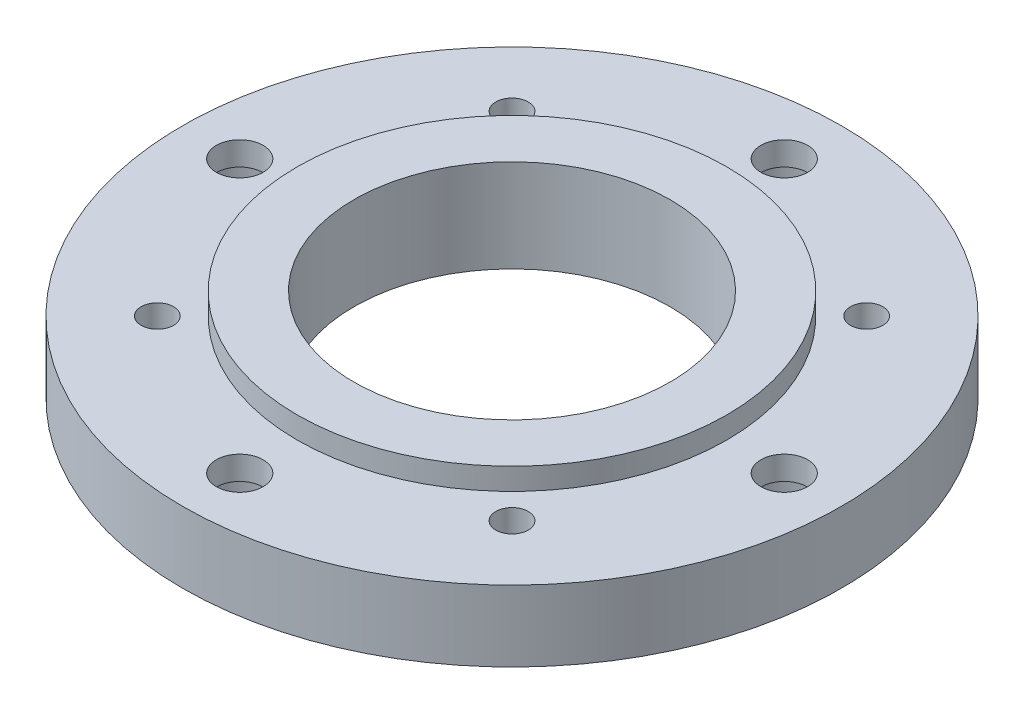
SolidWorks part; units mm, degrees
ref_plane "Front Plane" through (0, 0, 0) normal (0, 0, 1) x (1, 0, 0)
ref_plane "Top Plane" through (0, 0, 0) normal (0, 1, 0) x (1, 0, 0)
ref_plane "Right Plane" through (0, 0, 0) normal (1, 0, 0) x (0, 0, -1)
sketch "Sketch2" plane through (0, 0, 0) normal (0, 1, 0) x (1, 0, 0)
  line L0 (0, 22.985) -> (0, 0) construction
  line L1 (-12.3673, 12.3673) -> (0, 0) construction
  line L2 (0, 0) -> (12.3673, 12.3673) construction
  line L3 (0, 0) -> (12.3673, -12.3673) construction
  line L4 (0, 0) -> (-12.3673, -12.3673) construction
  circle A0 centre (0, 0) radius 22.985
  circle A1 centre (0, 0) radius 14.985
  circle A2 centre (0, 0) radius 11.025
  circle A3 centre (-12.3673, 12.3673) radius 1.13
  circle A4 centre (12.3673, 12.3673) radius 1.13
  circle A5 centre (-12.3673, -12.3673) radius 1.13
  circle A6 centre (12.3673, -12.3673) radius 1.13
  circle A7 centre (0, 18.99) radius 1.63
  circle A8 centre (18.99, 0) radius 1.63
  circle A9 centre (0, -18.99) radius 1.63
  circle A10 centre (-18.99, 0) radius 1.63
  point P14 (0, 0)
  point P15 (0, 0)
  point P16 (0, 0)
  point P25 (0, 0)
  point P26 (0, 0)
  point P27 (0, 0)
  point P28 (0, 0)
  point P29 (0, 0)
  point P30 (3.0189, -18.7485)
  point P31 (0, 0)
  dimension "D1" = 45.97
  dimension "D2" = 29.97
  dimension "D3" = 22.05
  dimension "D4" = 2.26
  dimension "D8" = 3.26
  dimension "D5" = 17.49
  dimension "D6" = 45
  dimension "D7" = 18.99
  dimension "D10" = 18.99
  dimension "D9" = 4
extrude "Boss-Extrude1" add sketch "Sketch2" along normal blind 4.95 contours A0 A10 A9 A8 A7 A6 A5 A4 A3 A1 | A1 A2 region at (-22.3349, 0, 0) region at (-14.5612, 0, 0)
extrude "Boss-Extrude2" add sketch "Sketch2<3>" along normal blind 1.52 from surface contours A1 A2 region at (-14.5612, 0, 0) starting at face at (-18.99, 4.95, 1.63)
sketch "Sketch2<3>" plane through (0, 0, 0) normal (0, 1, 0) x (1, 0, 0) same geometry as "Sketch2"
hole_wizard "#4-40 Tapped Hole1" positions "3DSketch1" profile "Sketch3" tap size "#4-40" standard "ANSI Inch" end condition through all
sketch3d "3DSketch1"
  line L0 (12.3673, 4.95, -12.3673) -> (12.3673, 0, -12.3673) construction
  line L1 (12.3673, 4.95, 12.3673) -> (12.3673, 0, 12.3673) construction
  line L2 (-12.3673, 4.95, 12.3673) -> (-12.3673, 0, 12.3673) construction
  line L7 (-12.3673, 4.95, -12.3673) -> (-12.3673, 0, -12.3673) construction
  point P13 (12.3673, 4.95, -12.3673)
  point P17 (12.3673, 4.95, 12.3673)
  point P21 (-12.3673, 4.95, 12.3673)
  point P51 (-12.3673, 4.95, -12.3673)
sketch "Sketch3" plane through (12.3673, 4.95, -12.3673) normal (1, 0, 0) x (0, 0, 1)
  line L0 (0, 0) -> (0, 4.95)
  line L1 (0, 4.95) -> (1.1303, 4.95)
  line L2 (1.1303, 4.95) -> (1.1303, 0)
  line L5 (1.1303, 0) -> (0, 0)
  line L11 (0, -6.35) -> (0, 107.95) construction
  dimension "Thru Tap Drill Dia." = 2.2606
  dimension "Thru Tap Drill Depth" = 4.95
cosmetic thread "Hole Thread2" parameters "D2"=2.8448
cosmetic thread "Hole Thread3" parameters "D2"=2.8448
cosmetic thread "Hole Thread4" parameters "D2"=2.8448
cosmetic thread "Hole Thread7" parameters "D2"=2.8448
hole_wizard "CBORE for #4 Socket Head Cap Screw1" positions "3DSketch2" profile "Sketch4" counterbore size "#4" standard "ANSI Inch" end condition through all
sketch3d "3DSketch2"
  line L0 (0, 4.95, 18.99) -> (0, 0, 18.99) construction
  line L1 (18.99, 4.95, 0) -> (18.99, 0, 0) construction
  line L2 (0, 4.95, -18.99) -> (0, 0, -18.99) construction
  line L3 (-18.99, 4.95, 0) -> (-18.99, 0, 0) construction
  point P0 (0, 0, 18.99)
  point P7 (18.99, 0, 0)
  point P11 (0, 0, -18.99)
  point P15 (-18.99, 0, 0)
sketch "Sketch4" plane through (0, 0, 18.99) normal (1, 0, 0) x (0, 0, -1)
  line L0 (0, 0) -> (0, 6.47)
  line L1 (0, 6.47) -> (1.6319, 6.47)
  line L3 (1.6319, 6.47) -> (1.6319, 3.3)
  line L4 (1.6319, 3.3) -> (3.225, 3.3)
  line L5 (3.225, 3.3) -> (3.225, 0)
  line L7 (3.225, 0) -> (0, 0)
  line L11 (0, -6.35) -> (0, 107.95) construction
  dimension "Thru Hole Dia." = 3.2639
  dimension "Thru Hole Depth" = 6.47
  dimension "C'Bore Dia." = 6.45
  dimension "C'Bore Depth" = 3.3
equation "\"D10@Sketch2\"=\"D7@Sketch2\""
